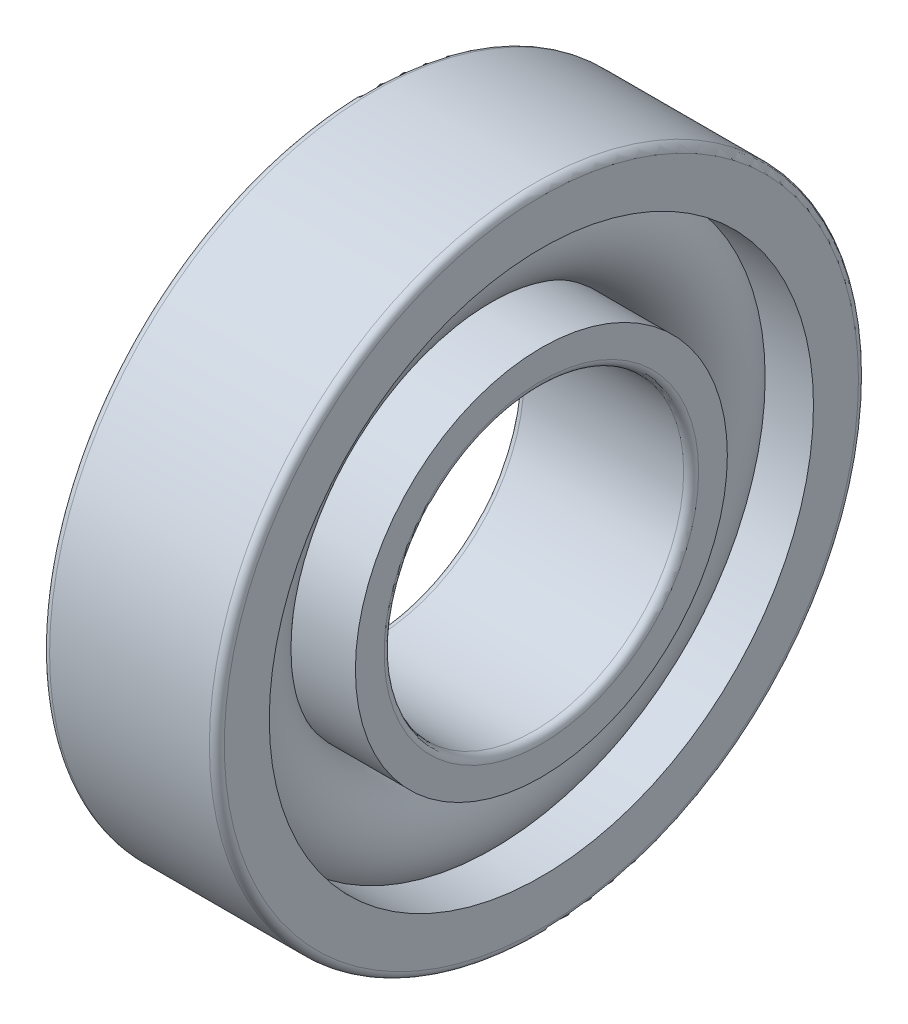
SolidWorks part; units mm, degrees
ref_plane "Plane1" through (0, 0, 0) normal (0, 0, 1) x (1, 0, 0)
ref_plane "Plane2" through (0, 0, 0) normal (0, 1, 0) x (1, 0, 0)
ref_plane "Plane3" through (0, 0, 0) normal (1, 0, 0) x (0, 0, -1)
other "Configuration Table"
sketch "Clipboard" plane through (0, 0, 0) normal (0, 0, 1) x (1, 0, 0)
  line L0 (-10, 0) -> (10, 0) construction
  line L1 (0, 0) -> (22.3471, -0.7804)
  line L2 (0, 0) -> (4.7471, 0.1658)
  line L3 (0, 0) -> (22.3471, -0.7804)
  line L4 (0, 0) -> (-22.3573, -0.3902)
  dimension "BallCLRad" = 4.75
sketch "CagSpiSke" plane through (0, 0, 0) normal (0, 0, 1) x (1, 0, 0)
  line L0 (0.2625, 4.575) -> (0.2625, 4.925)
  line L1 (0.2625, 4.925) -> (-0.2625, 4.925)
  line L2 (-0.2625, 4.925) -> (-0.2625, 4.575)
  line L3 (-0.2625, 4.575) -> (0.2625, 4.575)
  line L4 (-20.6375, 0) -> (20.6375, 0) construction
  line L5 (0, 0) -> (0, 23.7692) construction
  dimension "OD" = 9.85
  dimension "ID" = 9.15
revolve "CageSpine" add sketch "CagSpiSke" angle 0.001 about L4
ref_axis "Axis1" through (-50, 0, 0) along (1, 0, 0)
sketch "CagBalSke" plane through (0, 0, 0) normal (0, 0, 1) x (1, 0, 0)
  line L0 (-1.155, 4.75) -> (1.155, 4.75)
  line L1 (-1.905, 4.75) -> (1.905, 4.75) construction
  line L2 (-10, 0) -> (10, 0) construction
  line L3 (0, 0) -> (0, 24) construction
  arc A0 (1.155, 4.75) -> (-1.155, 4.75) centre (0, 4.75) cw
  dimension "BallCLRad" = 4.75
revolve "CageBall" [suppressed] add sketch "CagBalSke" angle 360 about L1 reverse direction yes
pattern_circular "CageBalls" [suppressed] count 2 every 180 about axis through (-50, 0, 0) along (1, 0, 0)
sketch "CagTrmODSke" plane through (0, 0, 0) normal (0, 0, 1) x (1, 0, 0)
  line L0 (1.156, 4.925) -> (1.156, 5.906)
  line L1 (1.156, 5.906) -> (-1.156, 5.906)
  line L2 (-1.156, 5.906) -> (-1.156, 4.925)
  line L3 (-1.156, 4.925) -> (1.156, 4.925)
  line L4 (-20.6375, 0) -> (20.6375, 0) construction
  line L5 (0, 0) -> (0, 25) construction
  dimension "Width" = 2.312
  dimension "ID" = 9.85
  dimension "OD" = 11.812
revolve "CageTrimOD" [suppressed] cut sketch "CagTrmODSke" angle 360 about L4 reverse direction yes
sketch "CagTrmIDSke" plane through (0, 0, 0) normal (0, 0, 1) x (1, 0, 0)
  line L0 (1.156, 3.596) -> (1.156, 4.575)
  line L1 (1.156, 4.575) -> (-1.156, 4.575)
  line L2 (-1.156, 4.575) -> (-1.156, 3.596)
  line L3 (-1.156, 3.596) -> (1.156, 3.596)
  line L4 (-20.6375, 0) -> (20.6375, 0) construction
  line L5 (0, 0) -> (0, 25) construction
  dimension "Width" = 2.312
  dimension "ID" = 7.192
  dimension "OD" = 9.15
revolve "CageTrimID" [suppressed] cut sketch "CagTrmIDSke" angle 360 about L4 reverse direction yes
sketch "BalSimSke" plane through (0, 0, 0) normal (0, 0, 1) x (1, 0, 0)
  line L0 (-10, 0) -> (10, 0) construction
  line L1 (-10, 4.75) -> (10, 4.75) construction
  line L2 (0, 0) -> (0, 23) construction
  circle A0 centre (0, 4.75) radius 1.05
  dimension "BallCLRad" = 4.75
  dimension "Ball_diameter" = 2.1
revolve "BallsSimplified" add sketch "BalSimSke" angle 360 about L0
sketch "BalDetSke" plane through (0, 0, 0) normal (0, 0, 1) x (1, 0, 0)
  line L0 (-1.05, 4.75) -> (1.05, 4.75)
  line L1 (-1.905, 4.75) -> (1.905, 4.75) construction
  line L2 (0, 0) -> (0, 25) construction
  arc A0 (1.05, 4.75) -> (-1.05, 4.75) centre (0, 4.75) cw
  dimension "BallCLRad" = 4.75
  dimension "Ball_diameter" = 2.1
revolve "BallDetailed" [suppressed] add sketch "BalDetSke" angle 360 about L1 reverse direction yes
sketch "InnRacSke" plane through (0, 0, 0) normal (0, 0, 1) x (1, 0, 0)
  line L0 (-0.7487, 4.05) -> (-1.75, 4.05)
  line L1 (-1.75, 4.05) -> (-1.75, 3.15)
  line L2 (-1.6, 3) -> (1.6, 3)
  line L3 (1.75, 3.15) -> (1.75, 3.725)
  line L4 (0, 3.725) -> (1.75, 3.725)
  line L5 (-20.6375, 0) -> (20.6375, 0) construction
  line L6 (0, 0) -> (0, 30) construction
  arc A0 (-1.75, 3.15) -> (-1.6, 3) centre (-1.6, 3.15) ccw
  arc A1 (1.6, 3) -> (1.75, 3.15) centre (1.6, 3.15) ccw
  arc A2 (0, 3.725) -> (-0.7487, 4.05) centre (0, 4.75) cw
  dimension "BallCLRad" = 4.75
  dimension "Fillet_radius" = 0.15
  dimension "Ball_diameter" = 2.05
  dimension "ID" = 6
  dimension "OD" = 8.1
  dimension "Width" = 3.5
revolve "InnerRace" add sketch "InnRacSke" angle 360 about L5 reverse direction yes
sketch "OutRacSke" plane through (0, 0, 0) normal (0, 0, 1) x (1, 0, 0)
  line L0 (0, 5.775) -> (-1.75, 5.775)
  line L1 (-1.75, 5.775) -> (-1.75, 6.35)
  line L2 (-1.6, 6.5) -> (1.6, 6.5)
  line L3 (1.75, 6.35) -> (1.75, 5.45)
  line L4 (1.75, 5.45) -> (0.7487, 5.45)
  line L5 (-20.6375, 0) -> (20.6375, 0) construction
  line L6 (0, 0) -> (0, 30) construction
  arc A0 (-1.75, 6.35) -> (-1.6, 6.5) centre (-1.6, 6.35) cw
  arc A1 (1.6, 6.5) -> (1.75, 6.35) centre (1.6, 6.35) cw
  arc A2 (0.7487, 5.45) -> (0, 5.775) centre (0, 4.75) ccw
  dimension "BallCLRad" = 4.75
  dimension "Fillet_radius" = 0.15
  dimension "Ball_diameter" = 2.05
  dimension "Width" = 3.5
revolve "OuterRace" add sketch "OutRacSke" angle 360 about L5 reverse direction yes
pattern_circular "BallsDetailed" [suppressed] count 2 every 180 about axis through (-50, 0, 0) along (1, 0, 0)
equation "\"BallCLRad@Clipboard\" = ( \"OD@OutRacSke\" + \"ID@InnRacSke\" ) / 4"
equation "\"BallCLRad@BalSimSke\" = \"BallCLRad@Clipboard\""
equation "\"BallCLRad@BalDetSke\" = \"BallCLRad@Clipboard\""
equation "\"BallCLRad@InnRacSke\" = \"BallCLRad@Clipboard\""
equation "\"BallCLRad@OutRacSke\" = \"BallCLRad@Clipboard\""
equation "\"Ball_diameter@InnRacSke\" = \"Ball_diameter@BalDetSke\" - 0.05"
equation "\"Ball_diameter@OutRacSke\" = \"Ball_diameter@BalDetSke\" - 0.05"
equation "\"Ball_diameter@BalSimSke\" = \"Ball_diameter@BalDetSke\""
equation "\"Width@OutRacSke\" = \"Width@InnRacSke\""
equation "\"Fillet_radius@OutRacSke\" = \"Fillet_radius@InnRacSke\""
equation "\"Max_count@Clipboard\" = int( 3.14159265 / atn(( \"Ball_diameter@BalDetSke\" / 2) / sqr( \"BallCLRad@Clipboard\"  *  \"BallCLRad@Clipboard\" - ( \"Ball_diameter@BalDetSke\" / 2) *  ( \"Ball_diameter@BalDetSke\" / 2))))"
equation "\"Max_count@Clipboard\" = ((sgn( \"Max_count@Clipboard\" - \"Count@Clipboard\" )-1)*( \"Max_count@Clipboard\" - \"Count@Clipboard\" ))/-2+ \"Count@Clipboard\""
equation "\"Count@BallsDetailed\" = int( \"Show_count@Clipboard\" ) "
equation "\"Count@BallsDetailed\" = ((sgn( \"Count@BallsDetailed\" - \"Max_count@Clipboard\" )-1)*( \"Count@BallsDetailed\" - \"Max_count@Clipboard\" ))/-2+ \"Max_count@Clipboard\""
equation "\"Count@BallsDetailed\" = ((sgn( \"Count@BallsDetailed\" - \"Min_count@Clipboard\" )+1)*( \"Count@BallsDetailed\" - \"Min_count@Clipboard\"))/2 +\"Min_count@Clipboard\""
equation "\"Angle@BallsDetailed\" = 360.0 / \"Max_count@Clipboard\""
equation "\"BallCLRad@CagBalSke\" = \"BallCLRad@Clipboard\""
equation "\"Count@CageBalls\" = \"Count@BallsDetailed\""
equation "\"Angle@CageBalls\" = \"Angle@BallsDetailed\""
equation "\"Angle@CageSpine\" =  \"Angle@CageBalls\" * ( \"Count@CageBalls\" -1 + int( \"Count@CageBalls\" / \"Max_count@Clipboard\" ) )  + 0.001 -  int( \"Count@CageBalls\" / \"Max_count@Clipboard\" ) * 0.001"
equation "\"Angle@CageSpine\" =  \"Angle@CageSpine\" * int( \"Min_count@Clipboard\" / 2) + int(1 / \"Min_count@Clipboard\")  * 0.001"
equation "\"CageWallOD@CagBalSke\" =  \"Ball_diameter@BalDetSke\" * 1.1"
equation "\"Thickness@CagSpiSke\" =  \"Ball_diameter@BalDetSke\" * 0.25"
equation "\"OD@CagTrmODSke\" = \"BallCLRad@Clipboard\" * 2 + \"CageWallOD@CagBalSke\" + 0.002"
equation "\"ID@CagTrmODSke\" = \"BallCLRad@Clipboard\" * 2 + \"Ball_diameter@BalDetSke\" / 6"
equation "\"OD@CagTrmIDSke\" = \"BallCLRad@Clipboard\" * 2 - \"Ball_diameter@BalDetSke\" / 6"
equation "\"ID@CagTrmIDSke\" = \"BallCLRad@Clipboard\" * 2 - \"CageWallOD@CagBalSke\" + 0.002"
equation "\"OD@CagSpiSke\" = \"ID@CagTrmODSke\""
equation "\"ID@CagSpiSke\" = \"OD@CagTrmIDSke\""
equation "\"Width@CagTrmODSke\" = \"CageWallOD@CagBalSke\" + 0.002"
equation "\"Width@CagTrmIDSke\" = \"CageWallOD@CagBalSke\" + 0.002"
